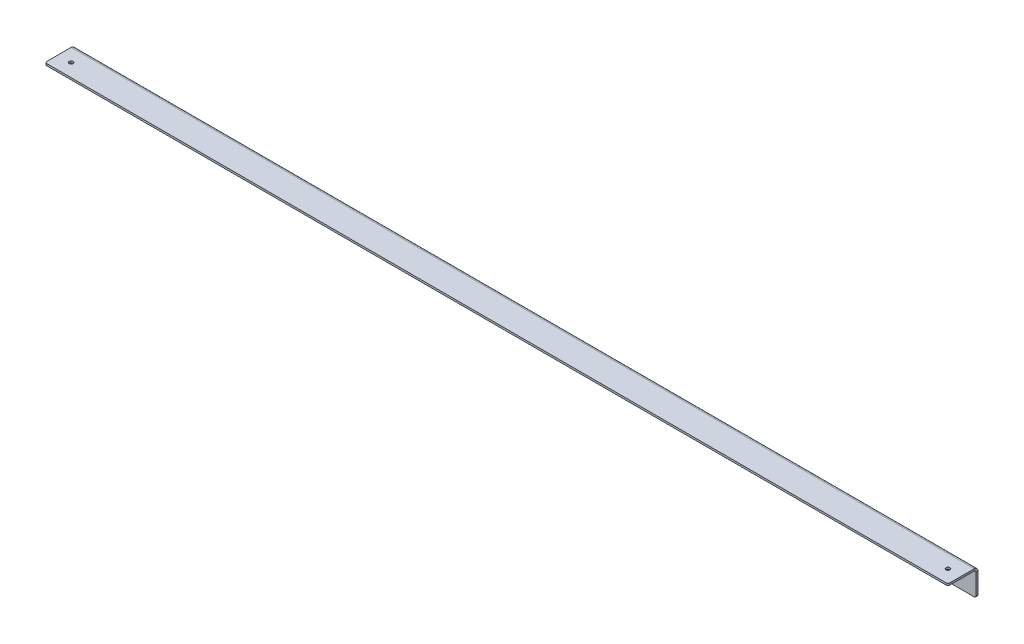
SolidWorks part; units mm, degrees
note: The reader was unsure of these and kept them because the rebuilt part matched: flange length of "Edge-Flange1".
material "5052-H32"
ref_plane "Front Plane" through (0, 0, 0) normal (0, 0, 1) x (1, 0, 0)
ref_plane "Top Plane" through (0, 0, 0) normal (0, 1, 0) x (1, 0, 0)
ref_plane "Right Plane" through (0, 0, 0) normal (1, 0, 0) x (0, 0, -1)
sketch "Sketch3" plane through (0, 0, 0) normal (0, 1, 0) x (1, 0, 0)
  line L1 (0, 0) -> (1530.35, 0)
  line L2 (0, 0) -> (0, 44.45)
  line L3 (0, 44.45) -> (1530.35, 44.45)
  line L4 (1530.35, 0) -> (1530.35, 44.45)
  line L5 (0, 0) -> (1530.35, 44.45) construction
  line L6 (0, 44.45) -> (1530.35, 0) construction
  point P4 (765.175, 22.225)
  dimension "D1" = 1530.35
  dimension "D2" = 44.45
base flange "Base-Flange1" sketch "Sketch3" thickness 3.2639 reverse thickness direction no parameters "D1"=6.35
edge flange "Edge-Flange1" sketch "Sketch10" flange angle 90 flange length 44.45 flange position bend outside bend radius 3.175 thickness 3.2639 relief rectangular parameters "D6"=10
sketch "Sketch10" plane through (0, -3.2639, -44.45) normal (0, 0, 1) x (-1, 0, 0)
  line L2 (-1530.35, 0) -> (-1530.35, 41.1861)
  line L3 (-1530.35, 41.1861) -> (0, 41.1861)
  line L4 (0, 41.1861) -> (0, 0)
  line L5 (0, 0) -> (-1530.35, 0) construction
  line L6 (0, 0) -> (-1530.35, 0)
bend "EdgeBend1" bend radius 3.175 bend angle 90 parameters "D5"=1
sketch "Sketch11" plane through (0, 0, 0) normal (0, 1, 0) x (1, 0, 0)
  line L1 (1508.125, 22.225) -> (1530.35, 22.225) construction
  line L2 (0, 44.45) -> (0, 0) construction
  line L4 (22.225, 22.225) -> (0, 22.225) construction
  line L8 (1530.35, 0) -> (1530.35, 44.45) construction
  circle A0 centre (1508.125, 22.225) radius 21.082 construction
  point P0 (22.225, 22.225)
  point P1 (1508.125, 22.225)
  dimension "D2" = 42.164
  dimension "D3" = 1485.9
hole_wizard "1/4 Clearance Hole1" positions "Sketch13" profile "Sketch12" hole size "1/4" standard "ANSI Inch" end condition through all
sketch "Sketch13" plane through (0, 0, 0) normal (0, 1, 0) x (1, 0, 0)
  point P0 (22.225, 22.225)
  point P3 (1508.125, 22.225)
sketch "Sketch12" plane through (22.225, 0, -22.225) normal (1, 0, 0) x (0, 0, 1)
  line L0 (0, 0) -> (0, 44.45)
  line L1 (0, 44.45) -> (3.3782, 44.45)
  line L2 (3.3782, 44.45) -> (3.3782, 0)
  line L5 (3.3782, 0) -> (0, 0)
  line L11 (0, -6.35) -> (0, 107.95) construction
  dimension "Thru Hole Dia." = 6.7564
  dimension "Thru Hole Depth" = 44.45
sketch "Sketch14" plane through (0, 0, 0) normal (0, 1, 0) x (1, 0, 0)
  line L0 (0, 0) -> (1530.35, 0) construction
  line L1 (0, 44.45) -> (0, 0) construction
  point P0 (257.175, 22.225)
  point P7 (358.775, 22.225)
  point P8 (460.375, 22.225)
  point P9 (561.975, 22.225)
  point P10 (663.575, 22.225)
  point P11 (765.175, 22.225)
  point P12 (866.775, 22.225)
  point P13 (968.375, 22.225)
  point P14 (1069.975, 22.225)
  point P15 (1171.575, 22.225)
  point P16 (1273.175, 22.225)
  dimension "D1" = 22.225
  dimension "D2" = 257.175
  dimension "D4" = 101.6
  dimension "D3" = 11
fillet "Fillet1" radius 3.175 4 edges at (0, -44.45, -49.257) (0, -1.632, 0) (1530.35, -44.45, -49.257) (1530.35, -1.632, 0)
sketch "Bend-Lines1" [suppressed] plane through (0, 0, 0) normal (0, 1, 0) x (1, 0, 0)
sketch "Bounding-Box1" [suppressed] plane through (0, 0, 0) normal (0, 1, 0) x (1, 0, 0)
sheet metal parameters "Sheet-Metal2" thickness 3.2639 parameters "D1"=6.35
flat pattern "Flat-Pattern2" [suppressed]
sketch "Bend-Lines2" plane through (0, 0, 0) normal (0, 1, 0) x (1, 0, 0)
sketch3d "Bounding-Box2" [suppressed]
  line L0 (-1530.35, 50.8, 0) -> (0, 50.8, 0) construction
  line L1 (-1530.35, 0, 0) -> (0, 0, 0) construction
  line L2 (-1530.35, 50.8, 0) -> (-1530.35, 0, 0) construction
  line L3 (0, 50.8, 0) -> (0, 0, 0) construction
sheet metal parameters "Sheet-Metal3" thickness 3.2639 parameters "D1"=6.35
flat pattern "Flat-Pattern2"
sketch "Bend-Lines2" plane through (0, 0, 0) normal (0, 1, 0) x (1, 0, 0)
  line L0 (1530.35, 55.88) -> (0, 55.88) construction
  line L1 (1530.35, 55.88) -> (0, 55.88) construction
sketch3d "Bounding-Box2" [suppressed]
  line L0 (1530.35, 98.9711, 0) -> (0, 98.9711, 0) construction
  line L1 (1530.35, 0, 0) -> (0, 0, 0) construction
  line L2 (1530.35, 98.9711, 0) -> (1530.35, 0, 0) construction
  line L3 (0, 98.9711, 0) -> (0, 0, 0) construction
bend of the flat pattern "Flatten-<EdgeBend1>1"
sheet metal parameters "Sheet-Metal4" thickness 3.2639 parameters "D1"=6.35
flat pattern "Flat-Pattern2"
sketch "Bend-Lines2" plane through (0, 0, 0) normal (0, 1, 0) x (1, 0, 0)
  line L0 (1530.35, 49.53) -> (0, 49.53) construction
  line L1 (1530.35, 49.53) -> (0, 49.53) construction
sketch3d "Bounding-Box2" [suppressed]
  line L0 (1530.35, 92.6211, 0) -> (0, 92.6211, 0) construction
  line L1 (1530.35, 0, 0) -> (0, 0, 0) construction
  line L2 (1530.35, 92.6211, 0) -> (1530.35, 0, 0) construction
  line L3 (0, 92.6211, 0) -> (0, 0, 0) construction
bend of the flat pattern "Flatten-<EdgeBend1>1"
